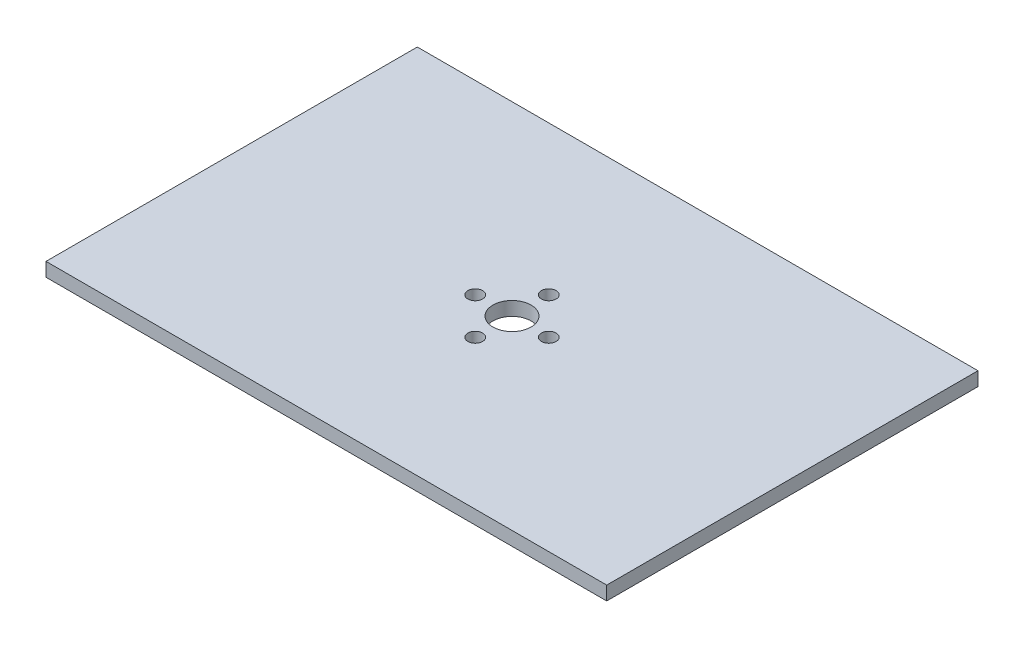
SolidWorks part; units mm, degrees
material "Carbon Fiber"
ref_plane "Front Plane" through (0, 0, 0) normal (0, 0, 1) x (1, 0, 0)
ref_plane "Top Plane" through (0, 0, 0) normal (0, 1, 0) x (1, 0, 0)
ref_plane "Right Plane" through (0, 0, 0) normal (1, 0, 0) x (0, 0, -1)
sketch "Sketch1" plane through (0, 0, 0) normal (0, 1, 0) x (1, 0, 0)
  line L0 (61, 80.79) -> (61, 0) construction
  line L1 (0, 0) -> (122, 0)
  line L2 (0, 0) -> (0, 80.79)
  line L3 (0, 80.79) -> (122, 80.79)
  line L4 (122, 0) -> (122, 80.79)
  line L5 (0, 40.395) -> (122, 40.395) construction
  circle A0 centre (53, 40.395) radius 1.6
  circle A1 centre (61, 48.395) radius 1.6
  circle A2 centre (69, 40.395) radius 1.6
  circle A3 centre (61, 32.395) radius 1.6
  circle A4 centre (61, 40.395) radius 4.15
  point P11 (61, 40.395)
  dimension "D3" = 3.2
  dimension "D4" = 8
  dimension "D6" = 8.3
  dimension "D1" = 122
  dimension "D2" = 80.79
  dimension "D5" = 4
extrude "Boss-Extrude1" add sketch "Sketch1" along normal blind 3
